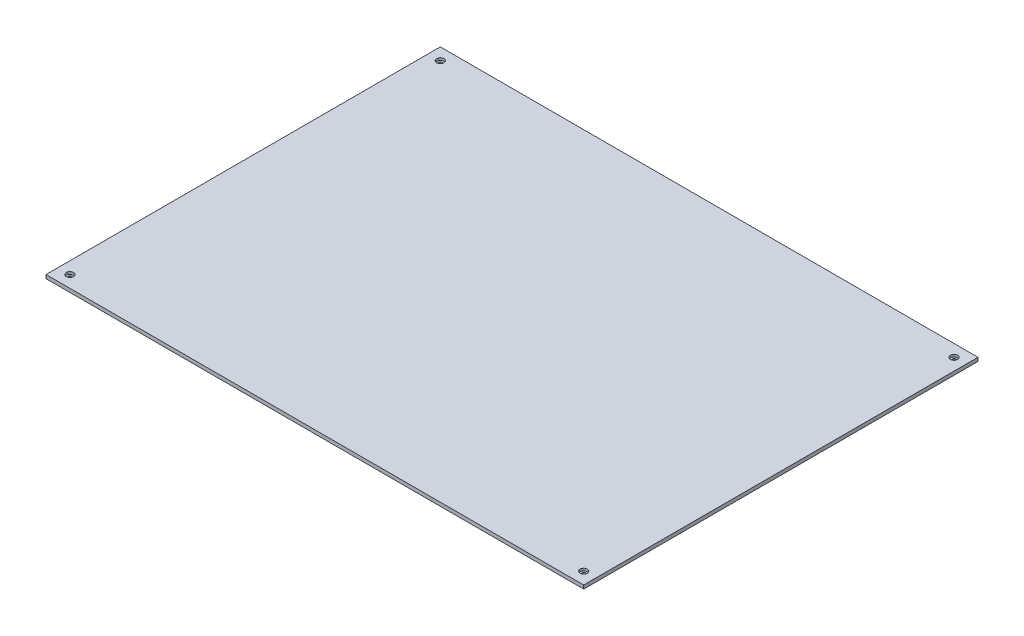
SolidWorks part; units mm, degrees
material "3003-O"
ref_plane "Front Plane" through (0, 0, 0) normal (0, 0, 1) x (1, 0, 0)
ref_plane "Top Plane" through (0, 0, 0) normal (0, 1, 0) x (1, 0, 0)
ref_plane "Right Plane" through (0, 0, 0) normal (1, 0, 0) x (0, 0, -1)
sketch "Sketch1" plane through (0, 0, 0) normal (0, 1, 0) x (1, 0, 0)
  line L1 (-225, -165) -> (225, -165)
  line L2 (-225, -165) -> (-225, 165)
  line L3 (-225, 165) -> (225, 165)
  line L4 (225, -165) -> (225, 165)
  line L5 (-225, -165) -> (225, 165) construction
  line L6 (-225, 165) -> (225, -165) construction
  line L11 (-1000, 0) -> (49000, 0) construction
  line L12 (0, -1000) -> (0, 49000) construction
  circle A0 centre (-215, 155) radius 1.55
  circle A1 centre (215, 155) radius 1.55
  circle A2 centre (-215, 155) radius 3.05
  circle A3 centre (215, 155) radius 3.05
  circle A4 centre (215, -155) radius 1.55
  circle A5 centre (215, -155) radius 3.05
  circle A6 centre (-215, -155) radius 1.55
  circle A7 centre (-215, -155) radius 3.05
  point P0 (0, 0)
  dimension "D3" = 3.1
  dimension "D6" = 6.1
  dimension "D1" = 450
  dimension "D2" = 330
  dimension "D4" = 10
  dimension "D5" = 10
extrude "Boss-Extrude1" add sketch "Sketch1" along normal blind 3 contours L1 L4 L3 L2 A5 A2 A3 A7 | A2 A0 | A3 A1 | A5 A4 | A7 A6 region at (0, 0, 0) region at (-217.9637, 0, -155) region at (212.0363, 0, -155) region at (212.0363, 0, 155) region at (-217.9637, 0, 155)
extrude "Cut-Extrude1" cut sketch "Sketch1<3>" against normal blind 2 from surface contours A7 A6 | A2 A0 | A5 A4 | A3 A1 region at (-217.9637, 0, -155) region at (212.0363, 0, -155) region at (212.0363, 0, 155) region at (-217.9637, 0, 155) starting at face at (0, 3, 0)
sketch "Sketch1<3>" plane through (0, 0, 0) normal (0, 1, 0) x (1, 0, 0) same geometry as "Sketch1"
